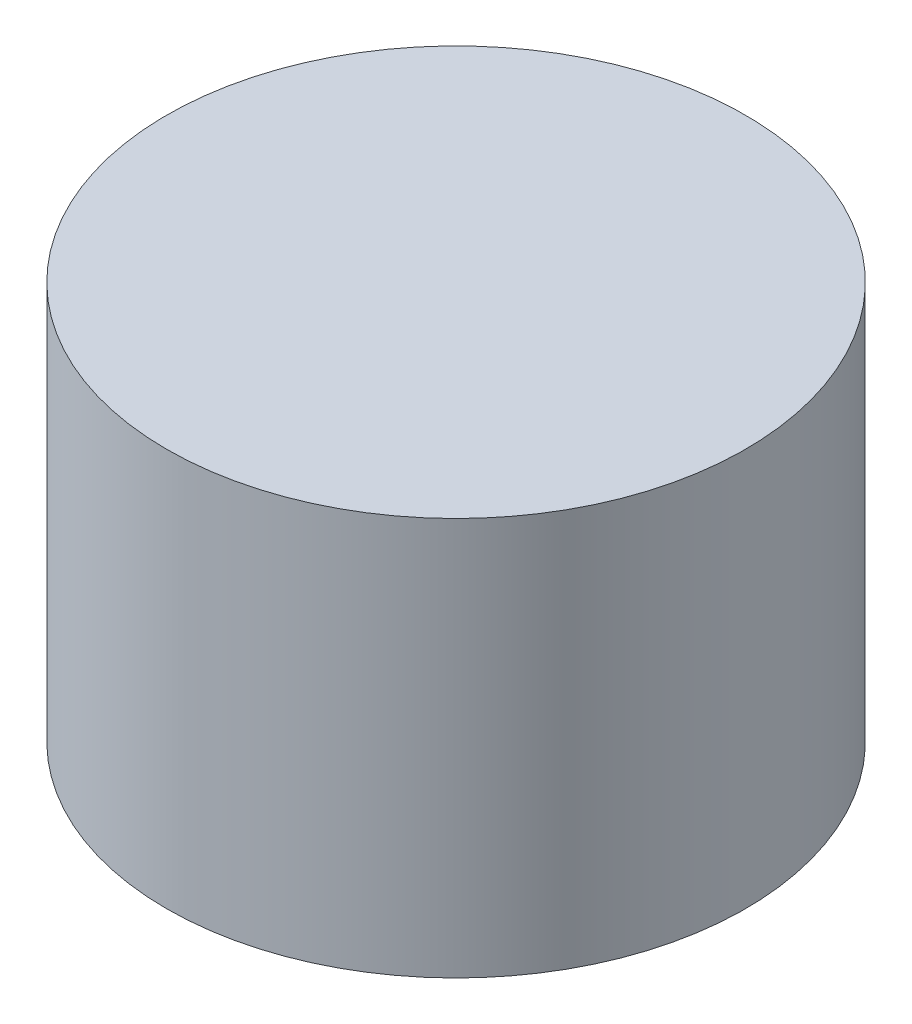
SolidWorks part; units mm, degrees
ref_plane "Top Plane" through (0, 0, 0) normal (0, 0, 1) x (1, 0, 0)
ref_plane "Right Plane" through (0, 0, 0) normal (0, 1, 0) x (1, 0, 0)
ref_plane "Front Plane" through (0, 0, 0) normal (1, 0, 0) x (0, 0, -1)
ref_axis "x-axis" through (-88.99, 0, 0) along (1, 0, 0)
ref_axis "y-axis" through (0, -55, 0) along (0, 1, 0)
ref_axis "z-axis" through (0, 0, 55) along (0, 0, -1)
sketch "Sketch1" plane through (0, 0, 0) normal (0, 1, 0) x (1, 0, 0)
  circle A0 centre (0, 0) radius 4
  dimension "D1" = 8
extrude "Boss-Extrude1" add sketch "Sketch1" against normal blind 5.5
